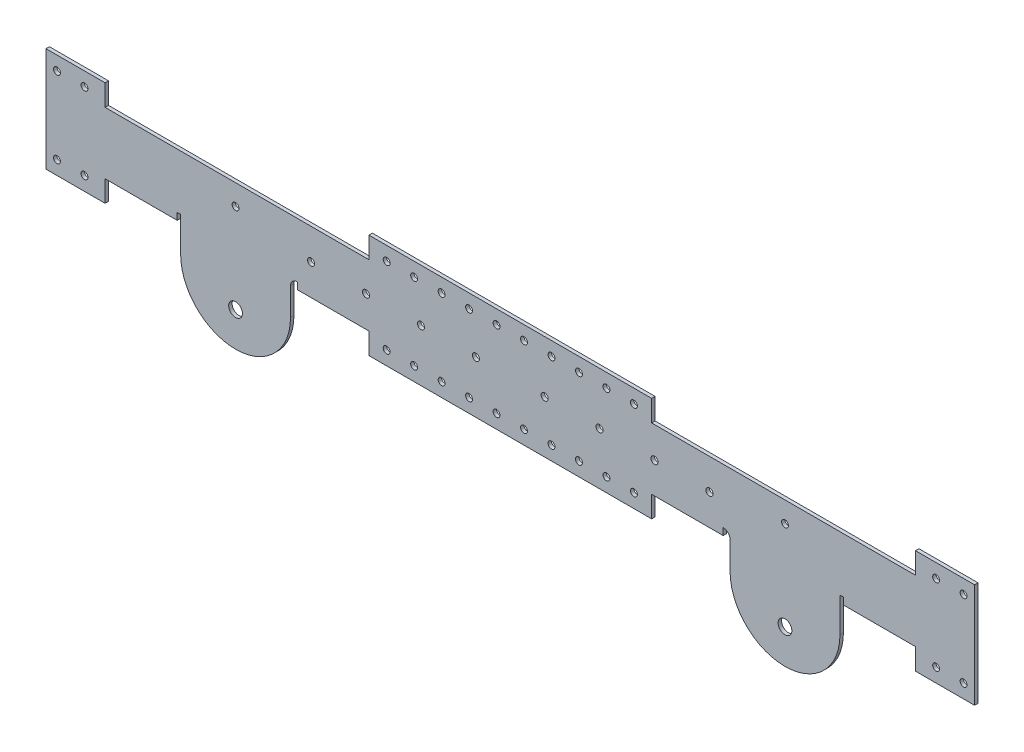
SolidWorks part; units mm, degrees
ref_plane "Front Plane" through (0, 0, 0) normal (0, 0, 1) x (1, 0, 0)
ref_plane "Top Plane" through (0, 0, 0) normal (0, 1, 0) x (1, 0, 0)
ref_plane "Right Plane" through (0, 0, 0) normal (1, 0, 0) x (0, 0, -1)
sketch "Sketch1" plane through (0, 0, 0) normal (0, 0, 1) x (1, 0, 0)
  line L0 (50.8, 0) -> (50.8, 25.4)
  line L1 (-50.8, 0) -> (-50.8, 76.2)
  line L2 (57.15, 31.75) -> (438.15, 31.75)
  line L3 (444.5, 25.4) -> (444.5, 0)
  line L4 (546.1, 0) -> (546.1, 76.2)
  line L5 (-50.8, 76.2) -> (546.1, 76.2)
  arc A0 (-50.8, 0) -> (50.8, 0) centre (0, 0) ccw
  arc A1 (50.8, 25.4) -> (57.15, 31.75) centre (57.15, 25.4) cw
  arc A2 (438.15, 31.75) -> (444.5, 25.4) centre (438.15, 25.4) cw
  arc A3 (444.5, 0) -> (546.1, 0) centre (495.3, 0) ccw
  circle A4 centre (0, 0) radius 6.35
  circle A5 centre (495.3, 0) radius 6.35
  dimension "D1" = 101.6
  dimension "D2" = 6.35
  dimension "D4" = 6.35
  dimension "D6" = 76.2
  dimension "D3" = 381
  dimension "D5" = 25.4
  dimension "D7" = 76.2
extrude "Boss-Extrude1" add sketch "Sketch1" along normal blind 3.175
sketch "Sketch2" plane through (0, 0, 3.175) normal (0, 0, 1) x (1, 0, 0)
  line L0 (-50.8, 76.2) -> (-50.8, 73.025)
  line L1 (-50.8, 76.2) -> (-50.8, 0) construction
  line L2 (546.1, 76.2) -> (-50.8, 76.2)
  line L3 (-50.8, 73.025) -> (546.1, 73.025)
  line L4 (546.1, 0) -> (546.1, 76.2) construction
  line L5 (546.1, 73.025) -> (546.1, 76.2)
  dimension "D1" = 3.175
extrude "Boss-Extrude2" add sketch "Sketch2" along normal blind 25.4
fillet "Fillet1" radius 2.54 2 edges at (247.65, 76.2, 0)
sketch "Sketch3" plane through (0, 76.2, 0) normal (0, 1, 0) x (1, 0, 0)
  line L0 (546.1, -28.575) -> (546.1, -2.54)
  circle A0 centre (527.05, -15.5575) radius 3.2639
  circle A1 centre (501.65, -15.5575) radius 3.2639
  circle A2 centre (476.25, -15.5575) radius 3.2639
  circle A3 centre (450.85, -15.5575) radius 3.2639
  circle A4 centre (425.45, -15.5575) radius 3.2639
  circle A5 centre (400.05, -15.5575) radius 3.2639
  circle A6 centre (374.65, -15.5575) radius 3.2639
  circle A7 centre (349.25, -15.5575) radius 3.2639
  circle A8 centre (323.85, -15.5575) radius 3.2639
  circle A9 centre (298.45, -15.5575) radius 3.2639
  circle A10 centre (273.05, -15.5575) radius 3.2639
  circle A11 centre (247.65, -15.5575) radius 3.2639
  circle A12 centre (222.25, -15.5575) radius 3.2639
  circle A13 centre (196.85, -15.5575) radius 3.2639
  circle A14 centre (171.45, -15.5575) radius 3.2639
  circle A15 centre (146.05, -15.5575) radius 3.2639
  circle A16 centre (120.65, -15.5575) radius 3.2639
  circle A17 centre (95.25, -15.5575) radius 3.2639
  circle A18 centre (69.85, -15.5575) radius 3.2639
  circle A19 centre (44.45, -15.5575) radius 3.2639
  circle A20 centre (19.05, -15.5575) radius 3.2639
  circle A21 centre (-6.35, -15.5575) radius 3.2639
  circle A22 centre (-31.75, -15.5575) radius 3.2639
  dimension "D1" = 19.05
  dimension "D2" = 23
extrude "Cut-Extrude1" cut sketch "Sketch3" against normal blind 25.4 contours A0 | A1 | A2 | A3 | A22 | A21 | A20 | A19 | A18 | A17 | A16 | A15 | A14 | A13 | A12 | A11 | A10 | A9 | A8 | A7 | A6 | A5 | A4 region at (527.05, 76.2, 15.5575) region at (501.65, 76.2, 15.5575) region at (476.25, 76.2, 15.5575) region at (450.85, 76.2, 15.5575) region at (425.45, 76.2, 15.5575) region at (400.05, 76.2, 15.5575) region at (374.65, 76.2, 15.5575) region at (349.25, 76.2, 15.5575) region at (323.85, 76.2, 15.5575) region at (298.45, 76.2, 15.5575) region at (273.05, 76.2, 15.5575) region at (247.65, 76.2, 15.5575) region at (222.25, 76.2, 15.5575) region at (196.85, 76.2, 15.5575) region at (171.45, 76.2, 15.5575) region at (146.05, 76.2, 15.5575) region at (120.65, 76.2, 15.5575) region at (95.25, 76.2, 15.5575) region at (69.85, 76.2, 15.5575) region at (44.45, 76.2, 15.5575) region at (19.05, 76.2, 15.5575) region at (-6.35, 76.2, 15.5575) region at (-31.75, 76.2, 15.5575)
sketch "Sketch5" plane through (0, 0, 0) normal (0, 0, -1) x (-1, 0, 0)
  line L0 (-444.5, 25.4) -> (-444.5, 0) construction
  circle A0 centre (-425.45, 53.975) radius 3.2639
  circle A1 centre (-374.65, 53.975) radius 3.2639
  circle A2 centre (-323.85, 53.975) radius 3.2639
  circle A3 centre (-273.05, 53.975) radius 3.2639
  circle A4 centre (-222.25, 53.975) radius 3.2639
  circle A5 centre (-171.45, 53.975) radius 3.2639
  circle A6 centre (-120.65, 53.975) radius 3.2639
  circle A7 centre (-69.85, 53.975) radius 3.2639
  dimension "D1" = 6.5278
  dimension "D2" = 19.05
  dimension "D3" = 8
extrude "Cut-Extrude2" cut sketch "Sketch5" against normal blind 25.4
sketch "Sketch6" plane through (0, 0, 3.175) normal (0, 0, 1) x (1, 0, 0)
  line L1 (-50.8, 76.2) -> (-82.55, 76.2)
  line L2 (-50.8, 76.2) -> (-50.8, 31.75)
  line L3 (-50.8, 31.75) -> (-82.55, 31.75)
  line L4 (-82.55, 76.2) -> (-82.55, 31.75)
  line L5 (546.1, 76.2) -> (577.85, 76.2)
  line L6 (546.1, 76.2) -> (546.1, 31.75)
  line L7 (546.1, 31.75) -> (577.85, 31.75)
  line L8 (577.85, 76.2) -> (577.85, 31.75)
  dimension "D1" = 31.75
  dimension "D2" = 31.75
extrude "Boss-Extrude3" add sketch "Sketch6" against normal blind 3.175
sketch "Sketch7" plane through (0, 0, 3.175) normal (0, 0, 1) x (1, 0, 0)
  line L1 (57.15, 31.75) -> (438.15, 31.75) construction
  line L2 (-50.8, 73.025) -> (-82.55, 73.025)
  line L3 (-50.8, 73.025) -> (-50.8, 76.2)
  line L4 (-50.8, 76.2) -> (-82.55, 76.2)
  line L5 (-82.55, 31.75) -> (-50.8, 31.75)
  line L6 (-82.55, 31.75) -> (-82.55, 34.925)
  line L7 (-82.55, 34.925) -> (-50.8, 34.925)
  line L8 (-50.8, 31.75) -> (-50.8, 34.925)
  line L9 (577.85, 31.75) -> (577.85, 76.2) construction
  line L10 (546.1, 76.2) -> (577.85, 76.2)
  line L11 (546.1, 76.2) -> (546.1, 73.025)
  line L12 (546.1, 73.025) -> (577.85, 73.025)
  line L13 (577.85, 76.2) -> (577.85, 73.025)
  line L14 (-82.55, 73.025) -> (-82.55, 76.2)
  line L15 (577.85, 31.75) -> (546.1, 31.75)
  line L16 (577.85, 31.75) -> (577.85, 34.925)
  line L17 (577.85, 34.925) -> (546.1, 34.925)
  line L18 (546.1, 31.75) -> (546.1, 34.925)
  line L19 (57.15, 31.75) -> (438.15, 31.75)
  line L20 (57.15, 31.75) -> (57.15, 34.925)
  line L21 (57.15, 34.925) -> (438.15, 34.925)
  line L22 (438.15, 31.75) -> (438.15, 34.925)
  arc A0 (57.15, 31.75) -> (50.8, 25.4) centre (57.15, 25.4) ccw construction
  dimension "D1" = 3.175
  dimension "D2" = 3.175
  dimension "D3" = 3.175
extrude "Boss-Extrude4" add sketch "Sketch7" along normal blind 25.4
fillet "Fillet2" radius 2.54 16 edges at (-50.8, 15.875, 0) (0, -50.8, 0) (50.8, 12.7, 0) (52.6599, 29.8901, 0) (546.1, 15.875, 0) (495.3, -50.8, 0) (444.5, 12.7, 0) (442.6401, 29.8901, 0) (-66.675, 34.925, 3.175) (-66.675, 31.75, 0) (247.65, 31.75, 0) (247.65, 34.925, 3.175) (561.975, 34.925, 3.175) (561.975, 31.75, 0) (561.975, 76.2, 0) (-66.675, 76.2, 0)
sketch "Sketch8" plane through (0, 76.2, 0) normal (0, 1, 0) x (1, 0, 0)
  circle A0 centre (-31.75, -15.5575) radius 3.2639 construction
  circle A1 centre (-31.75, -15.5575) radius 3.2639
  circle A2 centre (-57.15, -15.5575) radius 3.2639
  circle A3 centre (-31.75, -15.5575) radius 3.2639
  circle A4 centre (-6.35, -15.5575) radius 3.2639
  circle A5 centre (19.05, -15.5575) radius 3.2639
  circle A6 centre (44.45, -15.5575) radius 3.2639
  circle A7 centre (69.85, -15.5575) radius 3.2639
  circle A8 centre (95.25, -15.5575) radius 3.2639
  circle A9 centre (120.65, -15.5575) radius 3.2639
  circle A10 centre (146.05, -15.5575) radius 3.2639
  circle A11 centre (171.45, -15.5575) radius 3.2639
  circle A12 centre (196.85, -15.5575) radius 3.2639
  circle A13 centre (222.25, -15.5575) radius 3.2639
  circle A14 centre (247.65, -15.5575) radius 3.2639
  circle A15 centre (273.05, -15.5575) radius 3.2639
  circle A16 centre (298.45, -15.5575) radius 3.2639
  circle A17 centre (323.85, -15.5575) radius 3.2639
  circle A18 centre (349.25, -15.5575) radius 3.2639
  circle A19 centre (374.65, -15.5575) radius 3.2639
  circle A20 centre (400.05, -15.5575) radius 3.2639
  circle A21 centre (425.45, -15.5575) radius 3.2639
  circle A22 centre (450.85, -15.5575) radius 3.2639
  circle A23 centre (476.25, -15.5575) radius 3.2639
  circle A24 centre (501.65, -15.5575) radius 3.2639
  circle A25 centre (527.05, -15.5575) radius 3.2639
  circle A26 centre (-6.35, -15.5575) radius 3.2639
  circle A27 centre (19.05, -15.5575) radius 3.2639
  circle A28 centre (44.45, -15.5575) radius 3.2639
  circle A29 centre (69.85, -15.5575) radius 3.2639
  circle A30 centre (95.25, -15.5575) radius 3.2639
  circle A31 centre (120.65, -15.5575) radius 3.2639
  circle A32 centre (146.05, -15.5575) radius 3.2639
  circle A33 centre (171.45, -15.5575) radius 3.2639
  circle A34 centre (196.85, -15.5575) radius 3.2639
  circle A35 centre (222.25, -15.5575) radius 3.2639
  circle A36 centre (247.65, -15.5575) radius 3.2639
  circle A37 centre (273.05, -15.5575) radius 3.2639
  circle A38 centre (298.45, -15.5575) radius 3.2639
  circle A39 centre (323.85, -15.5575) radius 3.2639
  circle A40 centre (349.25, -15.5575) radius 3.2639
  circle A41 centre (374.65, -15.5575) radius 3.2639
  circle A42 centre (400.05, -15.5575) radius 3.2639
  circle A43 centre (425.45, -15.5575) radius 3.2639
  circle A44 centre (450.85, -15.5575) radius 3.2639
  circle A45 centre (476.25, -15.5575) radius 3.2639
  circle A46 centre (501.65, -15.5575) radius 3.2639
  circle A47 centre (527.05, -15.5575) radius 3.2639
  circle A48 centre (552.45, -15.5575) radius 3.2639
  circle M1 centre (425.45, -15.5575) radius 3.2639
  circle M2 centre (400.05, -15.5575) radius 3.2639
  circle M3 centre (374.65, -15.5575) radius 3.2639
  circle M4 centre (349.25, -15.5575) radius 3.2639
  circle M5 centre (323.85, -15.5575) radius 3.2639
  circle M6 centre (298.45, -15.5575) radius 3.2639
  circle M7 centre (273.05, -15.5575) radius 3.2639
  circle M8 centre (247.65, -15.5575) radius 3.2639
  circle M9 centre (222.25, -15.5575) radius 3.2639
  circle M10 centre (196.85, -15.5575) radius 3.2639
  circle M11 centre (171.45, -15.5575) radius 3.2639
  circle M12 centre (146.05, -15.5575) radius 3.2639
  circle M13 centre (120.65, -15.5575) radius 3.2639
  circle M14 centre (95.25, -15.5575) radius 3.2639
  circle M15 centre (69.85, -15.5575) radius 3.2639
  circle M16 centre (44.45, -15.5575) radius 3.2639
  circle M17 centre (19.05, -15.5575) radius 3.2639
  circle M18 centre (-6.35, -15.5575) radius 3.2639
  circle M19 centre (-31.75, -15.5575) radius 3.2639
  circle M20 centre (450.85, -15.5575) radius 3.2639
  circle M21 centre (476.25, -15.5575) radius 3.2639
  circle M22 centre (501.65, -15.5575) radius 3.2639
  circle M23 centre (527.05, -15.5575) radius 3.2639
  dimension "D1" = 2
  dimension "D2" = 24
extrude "Cut-Extrude3" cut sketch "Sketch8" against normal blind 177.8 contours A2 | M19 | M18 | M17 | M16 | M15 | M14 | M13 | M12 | M11 | M10 | M9 | M8 | M7 | M6 | M5 | M4 | M3 | M2 | M1 | M20 | M21 | A48 | M23 | M22 region at (-31.75, 76.2, 15.5575) region at (-57.15, 76.2, 15.5575) region at (-6.35, 76.2, 15.5575) region at (19.05, 76.2, 15.5575) region at (44.45, 76.2, 15.5575) region at (69.85, 76.2, 15.5575) region at (95.25, 76.2, 15.5575) region at (120.65, 76.2, 15.5575) region at (146.05, 76.2, 15.5575) region at (171.45, 76.2, 15.5575) region at (196.85, 76.2, 15.5575) region at (222.25, 76.2, 15.5575) region at (247.65, 76.2, 15.5575) region at (273.05, 76.2, 15.5575) region at (298.45, 76.2, 15.5575) region at (323.85, 76.2, 15.5575) region at (349.25, 76.2, 15.5575) region at (374.65, 76.2, 15.5575) region at (400.05, 76.2, 15.5575) region at (425.45, 76.2, 15.5575) region at (450.85, 76.2, 15.5575) region at (476.25, 76.2, 15.5575) region at (501.65, 76.2, 15.5575) region at (527.05, 76.2, 15.5575) region at (552.45, 76.2, 15.5575)
sketch "Sketch9" plane through (0, 76.2, 0) normal (0, 1, 0) x (1, 0, 0)
  line L0 (-82.55, -28.575) -> (298.45, -28.575)
  line L1 (577.85, -28.575) -> (-82.55, -28.575) construction
  line L3 (298.45, -28.575) -> (746.3929, -28.575)
  line L4 (298.45, -28.575) -> (298.45, 89.0041)
  line L5 (298.45, 89.0041) -> (746.3929, 89.0041)
  line L6 (746.3929, -28.575) -> (746.3929, 89.0041)
  circle M1 centre (552.45, -15.5575) radius 3.2639
  circle M3 centre (425.45, -15.5575) radius 3.2639
  circle M4 centre (400.05, -15.5575) radius 3.2639
  circle M5 centre (374.65, -15.5575) radius 3.2639
  circle M6 centre (349.25, -15.5575) radius 3.2639
  circle M7 centre (323.85, -15.5575) radius 3.2639
  circle M8 centre (298.45, -15.5575) radius 3.2639
  circle M22 centre (450.85, -15.5575) radius 3.2639
  circle M23 centre (476.25, -15.5575) radius 3.2639
  circle M24 centre (501.65, -15.5575) radius 3.2639
  circle M25 centre (527.05, -15.5575) radius 3.2639
  line M26 (577.85, -28.575) -> (577.85, -2.54)
  line M27 (577.85, -2.54) -> (546.1, -2.54)
  line M28 (546.1, -2.54) -> (-50.8, -2.54)
  line M31 (-82.55, -28.575) -> (577.85, -28.575)
extrude "Cut-Extrude5" cut sketch "Sketch9" against normal blind 432.308 contours L4 M31 M26 M27 M28 M8 M4 M6 M22 M24 M25 M23 M7 M5 M3 M1 | L3 L6 L5 L4 M28 M27 M26 region at (438.4843, 76.2, 15.5575) region at (535.9254, 76.2, -37.5492)
mirror "Mirror4" about plane through (298.45, -356.108, 0) normal (1, 0, 0) of bodies 110
sketch "Sketch10" plane through (-82.55, 0, 0) normal (-1, 0, 0) x (0, 0, 1)
  line L8 (0, 73.66) -> (0, 34.29)
  line L9 (2.54, 31.75) -> (28.575, 31.75)
  line L10 (28.575, 31.75) -> (28.575, 34.925)
  line L11 (28.575, 34.925) -> (5.715, 34.925)
  line L12 (3.175, 37.465) -> (3.175, 73.025)
  line L13 (3.175, 73.025) -> (28.575, 73.025)
  line L14 (28.575, 73.025) -> (28.575, 76.2)
  line L15 (28.575, 76.2) -> (2.54, 76.2)
  line L16 (0, 73.66) -> (0, 34.29)
  line L17 (2.54, 31.75) -> (28.575, 31.75)
  line L18 (28.575, 31.75) -> (28.575, 34.925)
  line L19 (28.575, 34.925) -> (5.715, 34.925)
  line L20 (3.175, 37.465) -> (3.175, 73.025)
  line L21 (3.175, 73.025) -> (28.575, 73.025)
  line L22 (28.575, 73.025) -> (28.575, 76.2)
  line L23 (28.575, 76.2) -> (2.54, 76.2)
  arc A3 (0, 34.29) -> (2.54, 31.75) centre (2.54, 34.29) ccw
  arc A4 (3.175, 37.465) -> (5.715, 34.925) centre (5.715, 37.465) ccw
  arc A5 (2.54, 76.2) -> (0, 73.66) centre (2.54, 73.66) ccw
  arc A6 (0, 34.29) -> (2.54, 31.75) centre (2.54, 34.29) ccw
  arc A7 (3.175, 37.465) -> (5.715, 34.925) centre (5.715, 37.465) ccw
  arc A8 (2.54, 76.2) -> (0, 73.66) centre (2.54, 73.66) ccw
  dimension "D1" = 0
extrude "Boss-Extrude6" add sketch "Sketch10" along normal blind 66.675
sketch "Sketch11" plane through (679.45, 0, 0) normal (1, 0, 0) x (0, 0, -1)
  line L8 (0, 34.29) -> (0, 73.66)
  line L9 (-2.54, 76.2) -> (-28.575, 76.2)
  line L10 (-28.575, 76.2) -> (-28.575, 73.025)
  line L11 (-28.575, 73.025) -> (-3.175, 73.025)
  line L12 (-3.175, 73.025) -> (-3.175, 37.465)
  line L13 (-5.715, 34.925) -> (-28.575, 34.925)
  line L14 (-28.575, 34.925) -> (-28.575, 31.75)
  line L15 (-28.575, 31.75) -> (-2.54, 31.75)
  line L16 (0, 34.29) -> (0, 73.66)
  line L17 (-2.54, 76.2) -> (-28.575, 76.2)
  line L18 (-28.575, 76.2) -> (-28.575, 73.025)
  line L19 (-28.575, 73.025) -> (-3.175, 73.025)
  line L20 (-3.175, 73.025) -> (-3.175, 37.465)
  line L21 (-5.715, 34.925) -> (-28.575, 34.925)
  line L22 (-28.575, 34.925) -> (-28.575, 31.75)
  line L23 (-28.575, 31.75) -> (-2.54, 31.75)
  arc A3 (0, 73.66) -> (-2.54, 76.2) centre (-2.54, 73.66) ccw
  arc A4 (-5.715, 34.925) -> (-3.175, 37.465) centre (-5.715, 37.465) ccw
  arc A5 (-2.54, 31.75) -> (0, 34.29) centre (-2.54, 34.29) ccw
  arc A6 (0, 73.66) -> (-2.54, 76.2) centre (-2.54, 73.66) ccw
  arc A7 (-5.715, 34.925) -> (-3.175, 37.465) centre (-5.715, 37.465) ccw
  arc A8 (-2.54, 31.75) -> (0, 34.29) centre (-2.54, 34.29) ccw
  dimension "D1" = 0
extrude "Boss-Extrude7" add sketch "Sketch11" along normal blind 66.675
sketch "Sketch12" plane through (0, 0, 3.175) normal (0, 0, 1) x (1, 0, 0)
  line L1 (114.3, 114.3) -> (-114.3, 114.3)
  line L2 (460.9211, 135.1062) -> (717.55, 135.1062)
  line L3 (460.9211, 135.1062) -> (460.9211, -117.6098)
  line L4 (482.6, 135.1062) -> (692.7253, 135.1062)
  line L5 (692.7253, 135.1062) -> (711.2, 135.1062)
  line L6 (460.9211, -117.6098) -> (717.55, -117.6098)
  line L7 (717.55, 135.1062) -> (717.55, -117.6098)
  line L8 (482.6, 135.1062) -> (460.9211, 135.1062)
  line L11 (460.9211, 135.1062) -> (460.9211, -59.2459)
  line L12 (711.2, 135.1062) -> (717.55, 135.1062)
  line L15 (717.55, 135.1062) -> (717.55, 3.7539)
  line L16 (114.3, 114.3) -> (135.9789, 114.3)
  line L17 (114.3, 0) -> (114.3, -15.4588)
  line L18 (114.3, -15.4588) -> (135.9789, -15.4588)
  line L19 (135.9789, 114.3) -> (135.9789, -15.4588)
  line L20 (-114.3, 114.3) -> (-120.65, 114.3)
  line L21 (-114.3, 0) -> (-114.3, -7.9863)
  line L22 (-114.3, -7.9863) -> (-120.65, -7.9863)
  line L23 (-120.65, 114.3) -> (-120.65, -7.9863)
  arc A0 (-114.3, 0) -> (114.3, 0) centre (0, 0) ccw
  circle M1 centre (0, 0) radius 6.35
  circle M5 centre (120.65, 53.975) radius 3.2639
  circle M6 centre (69.85, 53.975) radius 3.2639
  line M7 (57.15, 37.465) -> (539.75, 37.465)
  line M8 (539.75, 37.465) -> (539.75, 31.75)
  arc M9 (539.75, 31.75) -> (546.1, 25.4) centre (539.75, 25.4) cw
  line M10 (546.1, 25.4) -> (546.1, 0)
  arc M11 (546.1, 0) -> (647.7, 0) centre (596.9, 0) ccw
  line M12 (647.7, 0) -> (647.7, 31.75)
  line M13 (647.7, 31.75) -> (647.7, 37.465)
  line M14 (647.7, 37.465) -> (746.125, 37.465)
  line M16 (746.125, 73.025) -> (647.7, 73.025)
  line M17 (647.7, 73.025) -> (647.7, 70.485)
  line M18 (647.7, 70.485) -> (-50.8, 70.485)
  line M19 (-50.8, 70.485) -> (-50.8, 73.025)
  line M20 (-50.8, 73.025) -> (-149.225, 73.025)
  line M22 (-149.225, 37.465) -> (-50.8, 37.465)
  line M23 (-50.8, 37.465) -> (-50.8, 31.75)
  line M24 (-50.8, 31.75) -> (-50.8, 0)
  arc M25 (-50.8, 0) -> (50.8, 0) centre (0, 0) ccw
  line M26 (50.8, 0) -> (50.8, 25.4)
  arc M27 (50.8, 25.4) -> (57.15, 31.75) centre (57.15, 25.4) cw
  line M28 (57.15, 31.75) -> (57.15, 37.465)
  circle M29 centre (596.9, 0) radius 6.35
  circle M33 centre (476.25, 53.975) radius 3.2639
  circle M34 centre (527.05, 53.975) radius 3.2639
  dimension "D1" = 13.335
  dimension "D2" = 6.35
  dimension "D3" = 13.335
  dimension "D4" = 6.35
extrude "Cut-Extrude8" cut sketch "Sketch12" along normal blind 66.675 contours L7 L3 L6 M14 M13 M12 M11 M10 M9 M8 M7 | L7 L3 M16 M17 M18 M7 M8 M9 M10 M11 M12 M13 M14 M34 M33 M29 | L7 L2 L3 M18 M17 M16 | L21 A0 L17 L18 L19 L23 L22 M7 M28 M27 M26 M25 M24 M23 M22 | L23 L19 M20 M22 M23 M24 M25 M26 M27 M28 M7 M18 M19 M6 M5 M1 | L20 L23 L19 L16 L1 M20 M19 M18 region at (9.1616, 92.7234, 3.175) region at (2.7974, 27.6189, 3.175) region at (132.9974, 11.0031, 3.175) region at (594.1026, 27.6189, 3.175) region at (588.2256, 103.1313, 3.175) region at (500.3355, 34.4666, 3.175)
sketch "Sketch13" plane through (0, 76.2, 0) normal (0, 1, 0) x (1, 0, 0)
  circle A0 centre (146.05, -15.5575) radius 3.2639 construction
  circle A1 centre (146.05, -15.5575) radius 3.2639
sketch "Sketch14" plane through (746.125, 0, 0) normal (1, 0, 0) x (0, 0, -1)
  line L8 (0, 34.29) -> (0, 73.66)
  line L9 (-2.54, 76.2) -> (-28.575, 76.2)
  line L10 (-28.575, 76.2) -> (-28.575, 73.025)
  line L11 (-28.575, 73.025) -> (-3.175, 73.025)
  line L12 (-3.175, 73.025) -> (-3.175, 37.465)
  line L13 (-5.715, 34.925) -> (-28.575, 34.925)
  line L14 (-28.575, 34.925) -> (-28.575, 31.75)
  line L15 (-28.575, 31.75) -> (-2.54, 31.75)
  line L16 (0, 34.29) -> (0, 73.66)
  line L17 (-2.54, 76.2) -> (-28.575, 76.2)
  line L18 (-28.575, 76.2) -> (-28.575, 73.025)
  line L19 (-28.575, 73.025) -> (-3.175, 73.025)
  line L20 (-3.175, 73.025) -> (-3.175, 37.465)
  line L21 (-5.715, 34.925) -> (-28.575, 34.925)
  line L22 (-28.575, 34.925) -> (-28.575, 31.75)
  line L23 (-28.575, 31.75) -> (-2.54, 31.75)
  arc A3 (-2.54, 31.75) -> (0, 34.29) centre (-2.54, 34.29) ccw
  arc A4 (0, 73.66) -> (-2.54, 76.2) centre (-2.54, 73.66) ccw
  arc A5 (-5.715, 34.925) -> (-3.175, 37.465) centre (-5.715, 37.465) ccw
  arc A6 (-2.54, 31.75) -> (0, 34.29) centre (-2.54, 34.29) ccw
  arc A7 (0, 73.66) -> (-2.54, 76.2) centre (-2.54, 73.66) ccw
  arc A8 (-5.715, 34.925) -> (-3.175, 37.465) centre (-5.715, 37.465) ccw
  dimension "D1" = 0
extrude "Boss-Extrude8" add sketch "Sketch14" along normal blind 19.05
sketch "Sketch15" plane through (-149.225, 0, 0) normal (-1, 0, 0) x (0, 0, 1)
  line L8 (0, 73.66) -> (0, 34.29)
  line L9 (2.54, 31.75) -> (28.575, 31.75)
  line L10 (28.575, 31.75) -> (28.575, 34.925)
  line L11 (28.575, 34.925) -> (5.715, 34.925)
  line L12 (3.175, 37.465) -> (3.175, 73.025)
  line L13 (3.175, 73.025) -> (28.575, 73.025)
  line L14 (28.575, 73.025) -> (28.575, 76.2)
  line L15 (28.575, 76.2) -> (2.54, 76.2)
  line L16 (0, 73.66) -> (0, 34.29)
  line L17 (2.54, 31.75) -> (28.575, 31.75)
  line L18 (28.575, 31.75) -> (28.575, 34.925)
  line L19 (28.575, 34.925) -> (5.715, 34.925)
  line L20 (3.175, 37.465) -> (3.175, 73.025)
  line L21 (3.175, 73.025) -> (28.575, 73.025)
  line L22 (28.575, 73.025) -> (28.575, 76.2)
  line L23 (28.575, 76.2) -> (2.54, 76.2)
  arc A3 (2.54, 76.2) -> (0, 73.66) centre (2.54, 73.66) ccw
  arc A4 (0, 34.29) -> (2.54, 31.75) centre (2.54, 34.29) ccw
  arc A5 (3.175, 37.465) -> (5.715, 34.925) centre (5.715, 37.465) ccw
  arc A6 (2.54, 76.2) -> (0, 73.66) centre (2.54, 73.66) ccw
  arc A7 (0, 34.29) -> (2.54, 31.75) centre (2.54, 34.29) ccw
  arc A8 (3.175, 37.465) -> (5.715, 34.925) centre (5.715, 37.465) ccw
  dimension "D1" = 0
extrude "Boss-Extrude9" add sketch "Sketch15" along normal blind 19.05
sketch "Sketch16" plane through (0, 76.2, 0) normal (0, 1, 0) x (1, 0, 0)
  circle A0 centre (146.05, -15.5575) radius 3.2639 construction
  circle A1 centre (146.05, -15.5575) radius 3.2639
  circle A2 centre (171.45, -15.5575) radius 3.2639
  circle A3 centre (196.85, -15.5575) radius 3.2639
  circle A4 centre (222.25, -15.5575) radius 3.2639
  circle A5 centre (247.65, -15.5575) radius 3.2639
  circle A6 centre (273.05, -15.5575) radius 3.2639
  circle A7 centre (298.45, -15.5575) radius 3.2639
  circle A8 centre (323.85, -15.5575) radius 3.2639
  circle A9 centre (349.25, -15.5575) radius 3.2639
  circle A10 centre (374.65, -15.5575) radius 3.2639
  circle A11 centre (400.05, -15.5575) radius 3.2639
  circle A12 centre (425.45, -15.5575) radius 3.2639
  circle A13 centre (450.85, -15.5575) radius 3.2639
  circle A14 centre (476.25, -15.5575) radius 3.2639
  circle A15 centre (501.65, -15.5575) radius 3.2639
  circle A16 centre (527.05, -15.5575) radius 3.2639
  circle A17 centre (552.45, -15.5575) radius 3.2639
  circle A18 centre (577.85, -15.5575) radius 3.2639
  circle A19 centre (603.25, -15.5575) radius 3.2639
  circle A20 centre (628.65, -15.5575) radius 3.2639
  circle A21 centre (654.05, -15.5575) radius 3.2639
  circle A22 centre (679.45, -15.5575) radius 3.2639
  circle A23 centre (704.85, -15.5575) radius 3.2639
  circle A24 centre (730.25, -15.5575) radius 3.2639
  circle A25 centre (755.65, -15.5575) radius 3.2639
  circle A26 centre (146.05, -15.5575) radius 3.2639
  circle A27 centre (171.45, -15.5575) radius 3.2639
  circle A28 centre (196.85, -15.5575) radius 3.2639
  circle A29 centre (222.25, -15.5575) radius 3.2639
  circle A30 centre (247.65, -15.5575) radius 3.2639
  circle A31 centre (273.05, -15.5575) radius 3.2639
  circle A32 centre (298.45, -15.5575) radius 3.2639
  circle A33 centre (323.85, -15.5575) radius 3.2639
  circle A34 centre (349.25, -15.5575) radius 3.2639
  circle A35 centre (374.65, -15.5575) radius 3.2639
  circle A36 centre (400.05, -15.5575) radius 3.2639
  circle A37 centre (425.45, -15.5575) radius 3.2639
  circle A38 centre (450.85, -15.5575) radius 3.2639
  circle A39 centre (476.25, -15.5575) radius 3.2639
  circle A40 centre (501.65, -15.5575) radius 3.2639
  circle A41 centre (527.05, -15.5575) radius 3.2639
  circle A42 centre (552.45, -15.5575) radius 3.2639
  circle A43 centre (577.85, -15.5575) radius 3.2639
  circle A44 centre (603.25, -15.5575) radius 3.2639
  circle A45 centre (628.65, -15.5575) radius 3.2639
  circle A46 centre (654.05, -15.5575) radius 3.2639
  circle A47 centre (679.45, -15.5575) radius 3.2639
  circle A48 centre (704.85, -15.5575) radius 3.2639
  circle A49 centre (730.25, -15.5575) radius 3.2639
  circle A50 centre (120.65, -15.5575) radius 3.2639
  circle A51 centre (146.05, -15.5575) radius 3.2639
  circle A52 centre (171.45, -15.5575) radius 3.2639
  circle A53 centre (196.85, -15.5575) radius 3.2639
  circle A54 centre (222.25, -15.5575) radius 3.2639
  circle A55 centre (247.65, -15.5575) radius 3.2639
  circle A56 centre (273.05, -15.5575) radius 3.2639
  circle A57 centre (298.45, -15.5575) radius 3.2639
  circle A58 centre (323.85, -15.5575) radius 3.2639
  circle A59 centre (349.25, -15.5575) radius 3.2639
  circle A60 centre (374.65, -15.5575) radius 3.2639
  circle A61 centre (400.05, -15.5575) radius 3.2639
  circle A62 centre (425.45, -15.5575) radius 3.2639
  circle A63 centre (450.85, -15.5575) radius 3.2639
  circle A64 centre (476.25, -15.5575) radius 3.2639
  circle A65 centre (501.65, -15.5575) radius 3.2639
  circle A66 centre (527.05, -15.5575) radius 3.2639
  circle A67 centre (552.45, -15.5575) radius 3.2639
  circle A68 centre (577.85, -15.5575) radius 3.2639
  circle A69 centre (603.25, -15.5575) radius 3.2639
  circle A70 centre (628.65, -15.5575) radius 3.2639
  circle A71 centre (654.05, -15.5575) radius 3.2639
  circle A72 centre (679.45, -15.5575) radius 3.2639
  circle A73 centre (704.85, -15.5575) radius 3.2639
  circle A74 centre (95.25, -15.5575) radius 3.2639
  circle A75 centre (120.65, -15.5575) radius 3.2639
  circle A76 centre (146.05, -15.5575) radius 3.2639
  circle A77 centre (171.45, -15.5575) radius 3.2639
  circle A78 centre (196.85, -15.5575) radius 3.2639
  circle A79 centre (222.25, -15.5575) radius 3.2639
  circle A80 centre (247.65, -15.5575) radius 3.2639
  circle A81 centre (273.05, -15.5575) radius 3.2639
  circle A82 centre (298.45, -15.5575) radius 3.2639
  circle A83 centre (323.85, -15.5575) radius 3.2639
  circle A84 centre (349.25, -15.5575) radius 3.2639
  circle A85 centre (374.65, -15.5575) radius 3.2639
  circle A86 centre (400.05, -15.5575) radius 3.2639
  circle A87 centre (425.45, -15.5575) radius 3.2639
  circle A88 centre (450.85, -15.5575) radius 3.2639
  circle A89 centre (476.25, -15.5575) radius 3.2639
  circle A90 centre (501.65, -15.5575) radius 3.2639
  circle A91 centre (527.05, -15.5575) radius 3.2639
  circle A92 centre (552.45, -15.5575) radius 3.2639
  circle A93 centre (577.85, -15.5575) radius 3.2639
  circle A94 centre (603.25, -15.5575) radius 3.2639
  circle A95 centre (628.65, -15.5575) radius 3.2639
  circle A96 centre (654.05, -15.5575) radius 3.2639
  circle A97 centre (679.45, -15.5575) radius 3.2639
  circle A98 centre (69.85, -15.5575) radius 3.2639
  circle A99 centre (95.25, -15.5575) radius 3.2639
  circle A100 centre (120.65, -15.5575) radius 3.2639
  circle A101 centre (146.05, -15.5575) radius 3.2639
  circle A102 centre (171.45, -15.5575) radius 3.2639
  circle A103 centre (196.85, -15.5575) radius 3.2639
  circle A104 centre (222.25, -15.5575) radius 3.2639
  circle A105 centre (247.65, -15.5575) radius 3.2639
  circle A106 centre (273.05, -15.5575) radius 3.2639
  circle A107 centre (298.45, -15.5575) radius 3.2639
  circle A108 centre (323.85, -15.5575) radius 3.2639
  circle A109 centre (349.25, -15.5575) radius 3.2639
  circle A110 centre (374.65, -15.5575) radius 3.2639
  circle A111 centre (400.05, -15.5575) radius 3.2639
  circle A112 centre (425.45, -15.5575) radius 3.2639
  circle A113 centre (450.85, -15.5575) radius 3.2639
  circle A114 centre (476.25, -15.5575) radius 3.2639
  circle A115 centre (501.65, -15.5575) radius 3.2639
  circle A116 centre (527.05, -15.5575) radius 3.2639
  circle A117 centre (552.45, -15.5575) radius 3.2639
  circle A118 centre (577.85, -15.5575) radius 3.2639
  circle A119 centre (603.25, -15.5575) radius 3.2639
  circle A120 centre (628.65, -15.5575) radius 3.2639
  circle A121 centre (654.05, -15.5575) radius 3.2639
  circle A122 centre (44.45, -15.5575) radius 3.2639
  circle A123 centre (69.85, -15.5575) radius 3.2639
  circle A124 centre (95.25, -15.5575) radius 3.2639
  circle A125 centre (120.65, -15.5575) radius 3.2639
  circle A126 centre (146.05, -15.5575) radius 3.2639
  circle A127 centre (171.45, -15.5575) radius 3.2639
  circle A128 centre (196.85, -15.5575) radius 3.2639
  circle A129 centre (222.25, -15.5575) radius 3.2639
  circle A130 centre (247.65, -15.5575) radius 3.2639
  circle A131 centre (273.05, -15.5575) radius 3.2639
  circle A132 centre (298.45, -15.5575) radius 3.2639
  circle A133 centre (323.85, -15.5575) radius 3.2639
  circle A134 centre (349.25, -15.5575) radius 3.2639
  circle A135 centre (374.65, -15.5575) radius 3.2639
  circle A136 centre (400.05, -15.5575) radius 3.2639
  circle A137 centre (425.45, -15.5575) radius 3.2639
  circle A138 centre (450.85, -15.5575) radius 3.2639
  circle A139 centre (476.25, -15.5575) radius 3.2639
  circle A140 centre (501.65, -15.5575) radius 3.2639
  circle A141 centre (527.05, -15.5575) radius 3.2639
  circle A142 centre (552.45, -15.5575) radius 3.2639
  circle A143 centre (577.85, -15.5575) radius 3.2639
  circle A144 centre (603.25, -15.5575) radius 3.2639
  circle A145 centre (628.65, -15.5575) radius 3.2639
  circle A146 centre (19.05, -15.5575) radius 3.2639
  circle A147 centre (44.45, -15.5575) radius 3.2639
  circle A148 centre (69.85, -15.5575) radius 3.2639
  circle A149 centre (95.25, -15.5575) radius 3.2639
  circle A150 centre (120.65, -15.5575) radius 3.2639
  circle A151 centre (146.05, -15.5575) radius 3.2639
  circle A152 centre (171.45, -15.5575) radius 3.2639
  circle A153 centre (196.85, -15.5575) radius 3.2639
  circle A154 centre (222.25, -15.5575) radius 3.2639
  circle A155 centre (247.65, -15.5575) radius 3.2639
  circle A156 centre (273.05, -15.5575) radius 3.2639
  circle A157 centre (298.45, -15.5575) radius 3.2639
  circle A158 centre (323.85, -15.5575) radius 3.2639
  circle A159 centre (349.25, -15.5575) radius 3.2639
  circle A160 centre (374.65, -15.5575) radius 3.2639
  circle A161 centre (400.05, -15.5575) radius 3.2639
  circle A162 centre (425.45, -15.5575) radius 3.2639
  circle A163 centre (450.85, -15.5575) radius 3.2639
  circle A164 centre (476.25, -15.5575) radius 3.2639
  circle A165 centre (501.65, -15.5575) radius 3.2639
  circle A166 centre (527.05, -15.5575) radius 3.2639
  circle A167 centre (552.45, -15.5575) radius 3.2639
  circle A168 centre (577.85, -15.5575) radius 3.2639
  circle A169 centre (603.25, -15.5575) radius 3.2639
  circle A170 centre (-6.35, -15.5575) radius 3.2639
  circle A171 centre (19.05, -15.5575) radius 3.2639
  circle A172 centre (44.45, -15.5575) radius 3.2639
  circle A173 centre (69.85, -15.5575) radius 3.2639
  circle A174 centre (95.25, -15.5575) radius 3.2639
  circle A175 centre (120.65, -15.5575) radius 3.2639
  circle A176 centre (146.05, -15.5575) radius 3.2639
  circle A177 centre (171.45, -15.5575) radius 3.2639
  circle A178 centre (196.85, -15.5575) radius 3.2639
  circle A179 centre (222.25, -15.5575) radius 3.2639
  circle A180 centre (247.65, -15.5575) radius 3.2639
  circle A181 centre (273.05, -15.5575) radius 3.2639
  circle A182 centre (298.45, -15.5575) radius 3.2639
  circle A183 centre (323.85, -15.5575) radius 3.2639
  circle A184 centre (349.25, -15.5575) radius 3.2639
  circle A185 centre (374.65, -15.5575) radius 3.2639
  circle A186 centre (400.05, -15.5575) radius 3.2639
  circle A187 centre (425.45, -15.5575) radius 3.2639
  circle A188 centre (450.85, -15.5575) radius 3.2639
  circle A189 centre (476.25, -15.5575) radius 3.2639
  circle A190 centre (501.65, -15.5575) radius 3.2639
  circle A191 centre (527.05, -15.5575) radius 3.2639
  circle A192 centre (552.45, -15.5575) radius 3.2639
  circle A193 centre (577.85, -15.5575) radius 3.2639
  circle A194 centre (-31.75, -15.5575) radius 3.2639
  circle A195 centre (-6.35, -15.5575) radius 3.2639
  circle A196 centre (19.05, -15.5575) radius 3.2639
  circle A197 centre (44.45, -15.5575) radius 3.2639
  circle A198 centre (69.85, -15.5575) radius 3.2639
  circle A199 centre (95.25, -15.5575) radius 3.2639
  circle A200 centre (120.65, -15.5575) radius 3.2639
  circle A201 centre (146.05, -15.5575) radius 3.2639
  circle A202 centre (171.45, -15.5575) radius 3.2639
  circle A203 centre (196.85, -15.5575) radius 3.2639
  circle A204 centre (222.25, -15.5575) radius 3.2639
  circle A205 centre (247.65, -15.5575) radius 3.2639
  circle A206 centre (273.05, -15.5575) radius 3.2639
  circle A207 centre (298.45, -15.5575) radius 3.2639
  circle A208 centre (323.85, -15.5575) radius 3.2639
  circle A209 centre (349.25, -15.5575) radius 3.2639
  circle A210 centre (374.65, -15.5575) radius 3.2639
  circle A211 centre (400.05, -15.5575) radius 3.2639
  circle A212 centre (425.45, -15.5575) radius 3.2639
  circle A213 centre (450.85, -15.5575) radius 3.2639
  circle A214 centre (476.25, -15.5575) radius 3.2639
  circle A215 centre (501.65, -15.5575) radius 3.2639
  circle A216 centre (527.05, -15.5575) radius 3.2639
  circle A217 centre (552.45, -15.5575) radius 3.2639
  circle A218 centre (-57.15, -15.5575) radius 3.2639
  circle A219 centre (-31.75, -15.5575) radius 3.2639
  circle A220 centre (-6.35, -15.5575) radius 3.2639
  circle A221 centre (19.05, -15.5575) radius 3.2639
  circle A222 centre (44.45, -15.5575) radius 3.2639
  circle A223 centre (69.85, -15.5575) radius 3.2639
  circle A224 centre (95.25, -15.5575) radius 3.2639
  circle A225 centre (120.65, -15.5575) radius 3.2639
  circle A226 centre (146.05, -15.5575) radius 3.2639
  circle A227 centre (171.45, -15.5575) radius 3.2639
  circle A228 centre (196.85, -15.5575) radius 3.2639
  circle A229 centre (222.25, -15.5575) radius 3.2639
  circle A230 centre (247.65, -15.5575) radius 3.2639
  circle A231 centre (273.05, -15.5575) radius 3.2639
  circle A232 centre (298.45, -15.5575) radius 3.2639
  circle A233 centre (323.85, -15.5575) radius 3.2639
  circle A234 centre (349.25, -15.5575) radius 3.2639
  circle A235 centre (374.65, -15.5575) radius 3.2639
  circle A236 centre (400.05, -15.5575) radius 3.2639
  circle A237 centre (425.45, -15.5575) radius 3.2639
  circle A238 centre (450.85, -15.5575) radius 3.2639
  circle A239 centre (476.25, -15.5575) radius 3.2639
  circle A240 centre (501.65, -15.5575) radius 3.2639
  circle A241 centre (527.05, -15.5575) radius 3.2639
  circle A242 centre (-82.55, -15.5575) radius 3.2639
  circle A243 centre (-57.15, -15.5575) radius 3.2639
  circle A244 centre (-31.75, -15.5575) radius 3.2639
  circle A245 centre (-6.35, -15.5575) radius 3.2639
  circle A246 centre (19.05, -15.5575) radius 3.2639
  circle A247 centre (44.45, -15.5575) radius 3.2639
  circle A248 centre (69.85, -15.5575) radius 3.2639
  circle A249 centre (95.25, -15.5575) radius 3.2639
  circle A250 centre (120.65, -15.5575) radius 3.2639
  circle A251 centre (146.05, -15.5575) radius 3.2639
  circle A252 centre (171.45, -15.5575) radius 3.2639
  circle A253 centre (196.85, -15.5575) radius 3.2639
  circle A254 centre (222.25, -15.5575) radius 3.2639
  circle A255 centre (247.65, -15.5575) radius 3.2639
  circle A256 centre (273.05, -15.5575) radius 3.2639
  circle A257 centre (298.45, -15.5575) radius 3.2639
  circle A258 centre (323.85, -15.5575) radius 3.2639
  circle A259 centre (349.25, -15.5575) radius 3.2639
  circle A260 centre (374.65, -15.5575) radius 3.2639
  circle A261 centre (400.05, -15.5575) radius 3.2639
  circle A262 centre (425.45, -15.5575) radius 3.2639
  circle A263 centre (450.85, -15.5575) radius 3.2639
  circle A264 centre (476.25, -15.5575) radius 3.2639
  circle A265 centre (501.65, -15.5575) radius 3.2639
  circle A266 centre (-107.95, -15.5575) radius 3.2639
  circle A267 centre (-82.55, -15.5575) radius 3.2639
  circle A268 centre (-57.15, -15.5575) radius 3.2639
  circle A269 centre (-31.75, -15.5575) radius 3.2639
  circle A270 centre (-6.35, -15.5575) radius 3.2639
  circle A271 centre (19.05, -15.5575) radius 3.2639
  circle A272 centre (44.45, -15.5575) radius 3.2639
  circle A273 centre (69.85, -15.5575) radius 3.2639
  circle A274 centre (95.25, -15.5575) radius 3.2639
  circle A275 centre (120.65, -15.5575) radius 3.2639
  circle A276 centre (146.05, -15.5575) radius 3.2639
  circle A277 centre (171.45, -15.5575) radius 3.2639
  circle A278 centre (196.85, -15.5575) radius 3.2639
  circle A279 centre (222.25, -15.5575) radius 3.2639
  circle A280 centre (247.65, -15.5575) radius 3.2639
  circle A281 centre (273.05, -15.5575) radius 3.2639
  circle A282 centre (298.45, -15.5575) radius 3.2639
  circle A283 centre (323.85, -15.5575) radius 3.2639
  circle A284 centre (349.25, -15.5575) radius 3.2639
  circle A285 centre (374.65, -15.5575) radius 3.2639
  circle A286 centre (400.05, -15.5575) radius 3.2639
  circle A287 centre (425.45, -15.5575) radius 3.2639
  circle A288 centre (450.85, -15.5575) radius 3.2639
  circle A289 centre (476.25, -15.5575) radius 3.2639
  circle A290 centre (-133.35, -15.5575) radius 3.2639
  circle A291 centre (-107.95, -15.5575) radius 3.2639
  circle A292 centre (-82.55, -15.5575) radius 3.2639
  circle A293 centre (-57.15, -15.5575) radius 3.2639
  circle A294 centre (-31.75, -15.5575) radius 3.2639
  circle A295 centre (-6.35, -15.5575) radius 3.2639
  circle A296 centre (19.05, -15.5575) radius 3.2639
  circle A297 centre (44.45, -15.5575) radius 3.2639
  circle A298 centre (69.85, -15.5575) radius 3.2639
  circle A299 centre (95.25, -15.5575) radius 3.2639
  circle A300 centre (120.65, -15.5575) radius 3.2639
  circle A301 centre (146.05, -15.5575) radius 3.2639
  circle A302 centre (171.45, -15.5575) radius 3.2639
  circle A303 centre (196.85, -15.5575) radius 3.2639
  circle A304 centre (222.25, -15.5575) radius 3.2639
  circle A305 centre (247.65, -15.5575) radius 3.2639
  circle A306 centre (273.05, -15.5575) radius 3.2639
  circle A307 centre (298.45, -15.5575) radius 3.2639
  circle A308 centre (323.85, -15.5575) radius 3.2639
  circle A309 centre (349.25, -15.5575) radius 3.2639
  circle A310 centre (374.65, -15.5575) radius 3.2639
  circle A311 centre (400.05, -15.5575) radius 3.2639
  circle A312 centre (425.45, -15.5575) radius 3.2639
  circle A313 centre (450.85, -15.5575) radius 3.2639
  circle A314 centre (120.65, -15.5575) radius 3.2639
  circle A315 centre (95.25, -15.5575) radius 3.2639
  circle A316 centre (69.85, -15.5575) radius 3.2639
  circle A317 centre (44.45, -15.5575) radius 3.2639
  circle A318 centre (19.05, -15.5575) radius 3.2639
  circle A319 centre (-6.35, -15.5575) radius 3.2639
  circle A320 centre (-31.75, -15.5575) radius 3.2639
  circle A321 centre (-57.15, -15.5575) radius 3.2639
  circle A322 centre (-82.55, -15.5575) radius 3.2639
  circle A323 centre (-107.95, -15.5575) radius 3.2639
  circle A324 centre (-133.35, -15.5575) radius 3.2639
  circle A325 centre (-158.75, -15.5575) radius 3.2639
  dimension "D1" = 25
  dimension "D2" = 13
extrude "Cut-Extrude9" cut sketch "Sketch16" against normal blind 133.096
sketch "Sketch17" plane through (0, 0, 0) normal (0, 0, -1) x (-1, 0, 0)
  line L0 (-647.7, 76.2) -> (50.8, 76.2) construction
  circle A0 centre (0, 63.5) radius 3.175
  circle A1 centre (-596.9, 63.5) radius 3.175
  dimension "D1" = 12.7
extrude "Cut-Extrude11" cut sketch "Sketch17" against normal blind 5.08
sketch "Sketch18" plane through (0, 0, 3.175) normal (0, 0, 1) x (1, 0, 0)
  line L1 (-120.65, 73.025) -> (135.9789, 73.025)
  line L2 (-120.65, 73.025) -> (-120.65, 76.2)
  line L3 (-120.65, 76.2) -> (135.9789, 76.2)
  line L4 (135.9789, 73.025) -> (135.9789, 76.2)
  line L5 (460.9211, 76.2) -> (717.55, 76.2)
  line L6 (460.9211, 76.2) -> (460.9211, 73.025)
  line L7 (460.9211, 73.025) -> (717.55, 73.025)
  line L8 (717.55, 76.2) -> (717.55, 73.025)
  line L9 (717.55, 31.75) -> (-120.65, 31.75)
  line L10 (717.55, 31.75) -> (717.55, 34.925)
  line L11 (717.55, 34.925) -> (-120.65, 34.925)
  line L12 (-120.65, 31.75) -> (-120.65, 34.925)
extrude "Boss-Extrude10" add sketch "Sketch18" along normal blind 3.175
sketch "Sketch19" plane through (0, 0, 3.175) normal (0, 0, 1) x (1, 0, 0)
  line L0 (717.55, 34.925) -> (460.9211, 34.925) construction
  line L1 (-50.8, 31.75) -> (57.1504, 31.75)
  line L2 (-50.8, 31.75) -> (-50.8, 38.1387)
  line L3 (-50.8, 38.1387) -> (57.1504, 38.1387)
  line L4 (57.1504, 31.75) -> (57.1504, 38.1387)
  line L5 (647.7, 34.925) -> (539.75, 34.925)
  line L6 (647.7, 34.925) -> (647.7, 31.75)
  line L7 (647.7, 31.75) -> (539.75, 31.75)
  line L8 (539.75, 34.925) -> (539.75, 31.75)
extrude "Cut-Extrude12" cut sketch "Sketch19" along normal blind 3.175
sketch "Sketch20" plane through (0, 0, 0) normal (0, 0, -1) x (-1, 0, 0)
  line L0 (-342.9, 184.1305) -> (-342.9, -54.1947)
  line L2 (-342.9, 184.1305) -> (212.3723, 184.1305)
  line L3 (-342.9, 184.1305) -> (-342.9, -60.2979)
  line L4 (-342.9, -60.2979) -> (212.3723, -60.2979)
  line L5 (212.3723, 184.1305) -> (212.3723, -60.2979)
  circle A0 centre (-596.9, 0) radius 6.35 construction
  circle M3 centre (0, 63.5) radius 3.175
  circle M4 centre (0, 0) radius 6.35
  circle M5 centre (-273.05, 53.975) radius 3.2639
  circle M6 centre (-222.25, 53.975) radius 3.2639
  circle M7 centre (-171.45, 53.975) radius 3.2639
  circle M8 centre (-120.65, 53.975) radius 3.2639
  circle M9 centre (-69.85, 53.975) radius 3.2639
  line M10 (50.8, 73.66) -> (-647.7, 73.66)
  line M18 (-539.75, 34.29) -> (-57.15, 34.29)
  arc M19 (-57.15, 34.29) -> (-48.26, 25.4) centre (-57.15, 25.4) cw
  line M20 (-48.26, 25.4) -> (-48.26, 0)
  arc M21 (-48.26, 0) -> (48.26, 0) centre (0, 0) ccw
  line M22 (48.26, 0) -> (48.26, 34.29)
  line M23 (48.26, 34.29) -> (168.275, 34.29)
  line M24 (168.275, 34.29) -> (168.275, 73.66)
  line M25 (168.275, 73.66) -> (50.8, 73.66)
  circle M27 centre (-323.85, 53.975) radius 3.2639
  dimension "D1" = 254
extrude "Cut-Extrude13" cut sketch "Sketch20" against normal blind 277.622 contours L0 M10 M18 M19 M20 M21 M22 M23 M24 M25 M4 M6 M8 M27 M9 M7 M5 M3 | L5 L2 L0 L3 L4 M10 M25 M24 M23 M22 M21 M20 M19 M18 region at (65.2639, 178.0636, 0) region at (64.2403, 39.4662, 0)
sketch "Sketch21" plane through (0, 0, 3.175) normal (0, 0, 1) x (1, 0, 0)
  line L0 (546.1, 0) -> (546.1, 25.4) construction
  line L1 (647.7, 31.75) -> (647.7, 0) construction
  line L2 (546.1, 0) -> (546.1, 25.4)
  line L3 (647.7, 31.75) -> (647.7, 0)
  line L4 (539.75, 31.75) -> (539.75, 34.925)
  line L5 (539.75, 34.925) -> (647.7, 34.925)
  line L6 (647.7, 34.925) -> (647.7, 31.75)
  arc A0 (546.1, 25.4) -> (539.75, 31.75) centre (539.75, 25.4) ccw construction
  arc A1 (546.1, 0) -> (647.7, 0) centre (596.9, 0) ccw construction
  arc A2 (546.1, 25.4) -> (539.75, 31.75) centre (539.75, 25.4) ccw
  arc A3 (546.1, 0) -> (647.7, 0) centre (596.9, 0) ccw
  circle A4 centre (596.9, 0) radius 6.35 construction
  circle A5 centre (596.9, 0) radius 6.35
extrude "Boss-Extrude11" add sketch "Sketch21" against normal blind 3.175
mirror "Mirror5" about plane through (342.9, 0, 277.622) normal (1, 0, 0) of bodies 125
sketch "Sketch22" plane through (0, 76.2, 0) normal (0, 1, 0) x (1, 0, 0)
  line L0 (-79.375, -2.54) -> (-79.375, -28.575) construction
  line L1 (717.55, -6.35) -> (765.175, -6.35)
  line L2 (717.55, -6.35) -> (717.55, -28.575)
  line L3 (717.55, -28.575) -> (765.175, -28.575)
  line L4 (765.175, -6.35) -> (765.175, -28.575)
  line L5 (460.9211, -28.575) -> (224.8789, -28.575)
  line L6 (460.9211, -28.575) -> (460.9211, -6.35)
  line L7 (460.9211, -6.35) -> (224.8789, -6.35)
  line L8 (224.8789, -28.575) -> (224.8789, -6.35)
  line L9 (-31.75, -28.575) -> (-79.375, -28.575)
  line L10 (-31.75, -28.575) -> (-31.75, -6.35)
  line L11 (-31.75, -6.35) -> (-79.375, -6.35)
  line L12 (-79.375, -28.575) -> (-79.375, -6.35)
extrude "Boss-Extrude12" add sketch "Sketch22" against normal blind 3.175
sketch "Sketch23" plane through (0, 31.75, 0) normal (0, -1, 0) x (1, 0, 0)
  line L0 (765.175, 28.575) -> (765.175, 2.54) construction
  line L1 (-79.375, 28.575) -> (-31.75, 28.575)
  line L2 (-79.375, 28.575) -> (-79.375, 6.35)
  line L3 (-79.375, 6.35) -> (-31.75, 6.35)
  line L4 (-31.75, 28.575) -> (-31.75, 6.35)
  line L5 (224.8789, 28.575) -> (460.9211, 28.575)
  line L6 (224.8789, 28.575) -> (224.8789, 6.35)
  line L7 (224.8789, 6.35) -> (460.9211, 6.35)
  line L8 (460.9211, 28.575) -> (460.9211, 6.35)
  line L9 (717.55, 28.575) -> (765.175, 28.575)
  line L10 (717.55, 28.575) -> (717.55, 6.35)
  line L11 (717.55, 6.35) -> (765.175, 6.35)
  line L12 (765.175, 28.575) -> (765.175, 6.35)
extrude "Boss-Extrude14" add sketch "Sketch23" against normal blind 3.175
sketch "Sketch25" plane through (-79.375, 0, 0) normal (-1, 0, 0) x (0, 0, 1)
  line L8 (2.54, 31.75) -> (28.575, 31.75)
  line L9 (28.575, 31.75) -> (28.575, 34.925)
  line L10 (28.575, 34.925) -> (5.715, 34.925)
  line L11 (3.175, 37.465) -> (3.175, 73.025)
  line L12 (3.175, 73.025) -> (28.575, 73.025)
  line L13 (28.575, 73.025) -> (28.575, 76.2)
  line L14 (28.575, 76.2) -> (2.54, 76.2)
  line L15 (0, 73.66) -> (0, 34.29)
  line L16 (2.54, 31.75) -> (28.575, 31.75)
  line L17 (28.575, 31.75) -> (28.575, 34.925)
  line L18 (28.575, 34.925) -> (5.715, 34.925)
  line L19 (3.175, 37.465) -> (3.175, 73.025)
  line L20 (3.175, 73.025) -> (28.575, 73.025)
  line L21 (28.575, 73.025) -> (28.575, 76.2)
  line L22 (28.575, 76.2) -> (2.54, 76.2)
  line L23 (0, 73.66) -> (0, 34.29)
  arc A3 (0, 34.29) -> (2.54, 31.75) centre (2.54, 34.29) ccw
  arc A4 (3.175, 37.465) -> (5.715, 34.925) centre (5.715, 37.465) ccw
  arc A5 (2.54, 76.2) -> (0, 73.66) centre (2.54, 73.66) ccw
  arc A6 (0, 34.29) -> (2.54, 31.75) centre (2.54, 34.29) ccw
  arc A7 (3.175, 37.465) -> (5.715, 34.925) centre (5.715, 37.465) ccw
  arc A8 (2.54, 76.2) -> (0, 73.66) centre (2.54, 73.66) ccw
  dimension "D1" = 0
extrude "Boss-Extrude15" add sketch "Sketch25" along normal blind 12.7
sketch "Sketch26" plane through (765.175, 0, 0) normal (1, 0, 0) x (0, 0, -1)
  line L8 (-5.715, 34.925) -> (-28.575, 34.925)
  line L9 (-28.575, 34.925) -> (-28.575, 31.75)
  line L10 (-28.575, 31.75) -> (-2.54, 31.75)
  line L11 (0, 34.29) -> (0, 73.66)
  line L12 (-2.54, 76.2) -> (-28.575, 76.2)
  line L13 (-28.575, 76.2) -> (-28.575, 73.025)
  line L14 (-28.575, 73.025) -> (-3.175, 73.025)
  line L15 (-3.175, 73.025) -> (-3.175, 37.465)
  line L16 (-5.715, 34.925) -> (-28.575, 34.925)
  line L17 (-28.575, 34.925) -> (-28.575, 31.75)
  line L18 (-28.575, 31.75) -> (-2.54, 31.75)
  line L19 (0, 34.29) -> (0, 73.66)
  line L20 (-2.54, 76.2) -> (-28.575, 76.2)
  line L21 (-28.575, 76.2) -> (-28.575, 73.025)
  line L22 (-28.575, 73.025) -> (-3.175, 73.025)
  line L23 (-3.175, 73.025) -> (-3.175, 37.465)
  arc A3 (-2.54, 31.75) -> (0, 34.29) centre (-2.54, 34.29) ccw
  arc A4 (0, 73.66) -> (-2.54, 76.2) centre (-2.54, 73.66) ccw
  arc A5 (-5.715, 34.925) -> (-3.175, 37.465) centre (-5.715, 37.465) ccw
  arc A6 (-2.54, 31.75) -> (0, 34.29) centre (-2.54, 34.29) ccw
  arc A7 (0, 73.66) -> (-2.54, 76.2) centre (-2.54, 73.66) ccw
  arc A8 (-5.715, 34.925) -> (-3.175, 37.465) centre (-5.715, 37.465) ccw
  dimension "D1" = 0
extrude "Boss-Extrude16" add sketch "Sketch26" along normal blind 12.7
sketch "Sketch27" plane through (0, 76.2, 0) normal (0, 1, 0) x (1, 0, 0)
  line L0 (777.875, -2.54) -> (777.875, -28.575) construction
  circle A0 centre (762, -15.788) radius 3.175
  circle A1 centre (736.6, -15.788) radius 3.175
  circle A2 centre (711.2, -15.788) radius 3.175
  circle A3 centre (685.8, -15.788) radius 3.175
  circle A4 centre (660.4, -15.788) radius 3.175
  circle A5 centre (635, -15.788) radius 3.175
  circle A6 centre (609.6, -15.788) radius 3.175
  circle A7 centre (584.2, -15.788) radius 3.175
  circle A8 centre (558.8, -15.788) radius 3.175
  circle A9 centre (533.4, -15.788) radius 3.175
  circle A10 centre (508, -15.788) radius 3.175
  circle A11 centre (482.6, -15.788) radius 3.175
  circle A12 centre (457.2, -15.788) radius 3.175
  circle A13 centre (431.8, -15.788) radius 3.175
  circle A14 centre (406.4, -15.788) radius 3.175
  circle A15 centre (381, -15.788) radius 3.175
  circle A16 centre (355.6, -15.788) radius 3.175
  circle A17 centre (330.2, -15.788) radius 3.175
  circle A18 centre (304.8, -15.788) radius 3.175
  circle A19 centre (279.4, -15.788) radius 3.175
  circle A20 centre (254, -15.788) radius 3.175
  circle A21 centre (228.6, -15.788) radius 3.175
  circle A22 centre (203.2, -15.788) radius 3.175
  circle A23 centre (177.8, -15.788) radius 3.175
  circle A24 centre (152.4, -15.788) radius 3.175
  circle A25 centre (127, -15.788) radius 3.175
  circle A26 centre (101.6, -15.788) radius 3.175
  circle A27 centre (76.2, -15.788) radius 3.175
  circle A28 centre (50.8, -15.788) radius 3.175
  circle A29 centre (25.4, -15.788) radius 3.175
  circle A30 centre (0, -15.788) radius 3.175
  circle A31 centre (-25.4, -15.788) radius 3.175
  circle A32 centre (-50.8, -15.788) radius 3.175
  circle A33 centre (-76.2, -15.788) radius 3.175
  dimension "D1" = 15.875
  dimension "D2" = 34
extrude "Cut-Extrude15" cut sketch "Sketch27" against normal blind 76.2
sketch "Sketch28" plane through (224.8789, 0, 0) normal (-1, 0, 0) x (0, 0, 1)
  line L0 (18.963, 76.2) -> (12.613, 76.2) construction
  line L1 (18.963, 76.2) -> (12.613, 76.2)
  line L6 (6.35, 76.2) -> (6.35, 73.025)
  line L7 (6.35, 73.025) -> (28.575, 73.025)
  line L8 (28.575, 73.025) -> (28.575, 76.2)
  line L9 (28.575, 76.2) -> (6.35, 76.2)
  line L10 (6.35, 76.2) -> (6.35, 73.025)
  line L11 (6.35, 73.025) -> (28.575, 73.025)
  line L12 (28.575, 73.025) -> (28.575, 76.2)
  line L13 (28.575, 76.2) -> (6.35, 76.2)
  line L14 (6.35, 34.925) -> (6.35, 31.75)
  line L15 (6.35, 31.75) -> (28.575, 31.75)
  line L16 (28.575, 31.75) -> (28.575, 34.925)
  line L17 (28.575, 34.925) -> (6.35, 34.925)
  line L18 (6.35, 34.925) -> (6.35, 31.75)
  line L19 (6.35, 31.75) -> (28.575, 31.75)
  line L20 (28.575, 31.75) -> (28.575, 34.925)
  line L21 (28.575, 34.925) -> (6.35, 34.925)
  line M9 (6.35, 76.2) -> (6.35, 73.025)
  line M10 (6.35, 73.025) -> (28.575, 73.025)
  line M11 (28.575, 73.025) -> (28.575, 76.2)
  line M12 (28.575, 76.2) -> (6.35, 76.2)
  dimension "D1" = 0
  dimension "D2" = 0
extrude "Boss-Extrude17" add sketch "Sketch28" along normal blind 12.7 contours L20 L21 L18 L19 | M12 M9 M10 M11 region at (224.8789, 74.6125, 17.4625) region at (224.8789, 33.3375, 17.4625)
sketch "Sketch29" plane through (460.9211, 0, 0) normal (1, 0, 0) x (0, 0, -1)
  line L4 (-6.35, 73.025) -> (-6.35, 76.2)
  line L5 (-6.35, 76.2) -> (-28.575, 76.2)
  line L6 (-28.575, 76.2) -> (-28.575, 73.025)
  line L7 (-28.575, 73.025) -> (-6.35, 73.025)
  line L8 (-6.35, 73.025) -> (-6.35, 76.2)
  line L9 (-6.35, 76.2) -> (-28.575, 76.2)
  line L10 (-28.575, 76.2) -> (-28.575, 73.025)
  line L11 (-28.575, 73.025) -> (-6.35, 73.025)
  line L12 (-6.35, 31.75) -> (-6.35, 34.925)
  line L13 (-6.35, 34.925) -> (-28.575, 34.925)
  line L14 (-28.575, 34.925) -> (-28.575, 31.75)
  line L15 (-28.575, 31.75) -> (-6.35, 31.75)
  line L16 (-6.35, 31.75) -> (-6.35, 34.925)
  line L17 (-6.35, 34.925) -> (-28.575, 34.925)
  line L18 (-28.575, 34.925) -> (-28.575, 31.75)
  line L19 (-28.575, 31.75) -> (-6.35, 31.75)
  dimension "D1" = 0
  dimension "D2" = 0
extrude "Boss-Extrude18" add sketch "Sketch29" along normal blind 12.7
sketch "Sketch30" plane through (0, 0, 3.175) normal (0, 0, 1) x (1, 0, 0)
  line L0 (-31.75, 76.2) -> (212.1789, 76.2) construction
  line L1 (71.8679, 15.0245) -> (76.6895, -7.5765)
  line L2 (76.6895, -7.5765) -> (114.0564, -16.0142)
  line L3 (114.0564, -16.0142) -> (104.112, 17.1339)
  line L4 (104.112, 17.1339) -> (71.8679, 15.0245)
  circle A0 centre (87.6482, -19.05) radius 6.3215
  dimension "D1" = 95.25
extrude "Boss-Extrude19" add sketch "Sketch30" against normal blind 3.175
sketch "Sketch31" plane through (0, 0, 3.175) normal (0, 0, 1) x (1, 0, 0)
  line L0 (-31.75, 76.2) -> (212.1789, 76.2) construction
  line L1 (342.9, 0) -> (342.9, -45.6117)
  circle A0 centre (88.9, -19.05) radius 6.35
  arc A1 (38.1, 0) -> (139.7, 0) centre (88.9, 0) ccw construction
  circle A2 centre (596.9, -19.05) radius 6.35
  point P6 (88.9, -50.8)
  dimension "D1" = 95.25
  dimension "D2" = 254
extrude "Cut-Extrude16" cut sketch "Sketch31" against normal blind 3.175 contours A0 | A2 region at (88.9, -19.05, 3.175) region at (596.9, -19.05, 3.175)
sketch "Sketch32" plane through (0, 0, 3.175) normal (0, 0, 1) x (1, 0, 0)
  line L1 (586.7711, 11.0985) -> (615.3458, 11.0985)
  line L2 (586.7711, 11.0985) -> (586.7711, -7.6012)
  line L3 (586.7711, -7.6012) -> (615.3458, -7.6012)
  line L4 (615.3458, 11.0985) -> (615.3458, -7.6012)
extrude "Boss-Extrude20" add sketch "Sketch32" against normal blind 3.175
sketch "Sketch33" plane through (-92.075, 0, 0) normal (-1, 0, 0) x (0, 0, 1)
  line L8 (2.54, 31.75) -> (28.575, 31.75)
  line L9 (28.575, 31.75) -> (28.575, 34.925)
  line L10 (28.575, 34.925) -> (5.715, 34.925)
  line L11 (3.175, 37.465) -> (3.175, 73.025)
  line L12 (3.175, 73.025) -> (28.575, 73.025)
  line L13 (28.575, 73.025) -> (28.575, 76.2)
  line L14 (28.575, 76.2) -> (2.54, 76.2)
  line L15 (0, 73.66) -> (0, 34.29)
  line L16 (2.54, 31.75) -> (28.575, 31.75)
  line L17 (28.575, 31.75) -> (28.575, 34.925)
  line L18 (28.575, 34.925) -> (5.715, 34.925)
  line L19 (3.175, 37.465) -> (3.175, 73.025)
  line L20 (3.175, 73.025) -> (28.575, 73.025)
  line L21 (28.575, 73.025) -> (28.575, 76.2)
  line L22 (28.575, 76.2) -> (2.54, 76.2)
  line L23 (0, 73.66) -> (0, 34.29)
  arc A3 (0, 34.29) -> (2.54, 31.75) centre (2.54, 34.29) ccw
  arc A4 (3.175, 37.465) -> (5.715, 34.925) centre (5.715, 37.465) ccw
  arc A5 (2.54, 76.2) -> (0, 73.66) centre (2.54, 73.66) ccw
  arc A6 (0, 34.29) -> (2.54, 31.75) centre (2.54, 34.29) ccw
  arc A7 (3.175, 37.465) -> (5.715, 34.925) centre (5.715, 37.465) ccw
  arc A8 (2.54, 76.2) -> (0, 73.66) centre (2.54, 73.66) ccw
  dimension "D1" = 0
extrude "Cut-Extrude17" cut sketch "Sketch33" against normal blind 5.715
sketch "Sketch34" plane through (777.875, 0, 0) normal (1, 0, 0) x (0, 0, -1)
  line L8 (-5.715, 34.925) -> (-28.575, 34.925)
  line L9 (-28.575, 34.925) -> (-28.575, 31.75)
  line L10 (-28.575, 31.75) -> (-2.54, 31.75)
  line L11 (0, 34.29) -> (0, 73.66)
  line L12 (-2.54, 76.2) -> (-28.575, 76.2)
  line L13 (-28.575, 76.2) -> (-28.575, 73.025)
  line L14 (-28.575, 73.025) -> (-3.175, 73.025)
  line L15 (-3.175, 73.025) -> (-3.175, 37.465)
  line L16 (-5.715, 34.925) -> (-28.575, 34.925)
  line L17 (-28.575, 34.925) -> (-28.575, 31.75)
  line L18 (-28.575, 31.75) -> (-2.54, 31.75)
  line L19 (0, 34.29) -> (0, 73.66)
  line L20 (-2.54, 76.2) -> (-28.575, 76.2)
  line L21 (-28.575, 76.2) -> (-28.575, 73.025)
  line L22 (-28.575, 73.025) -> (-3.175, 73.025)
  line L23 (-3.175, 73.025) -> (-3.175, 37.465)
  arc A3 (-5.715, 34.925) -> (-3.175, 37.465) centre (-5.715, 37.465) ccw
  arc A4 (-2.54, 31.75) -> (0, 34.29) centre (-2.54, 34.29) ccw
  arc A5 (0, 73.66) -> (-2.54, 76.2) centre (-2.54, 73.66) ccw
  arc A6 (-5.715, 34.925) -> (-3.175, 37.465) centre (-5.715, 37.465) ccw
  arc A7 (-2.54, 31.75) -> (0, 34.29) centre (-2.54, 34.29) ccw
  arc A8 (0, 73.66) -> (-2.54, 76.2) centre (-2.54, 73.66) ccw
  dimension "D1" = 0
extrude "Cut-Extrude18" cut sketch "Sketch34" against normal blind 5.715
sketch "Sketch35" plane through (0, 0, 3.175) normal (0, 0, 1) x (1, 0, 0)
  line L0 (650.875, 34.925) -> (650.875, 25.4)
  line L1 (-86.36, 73.025) -> (772.16, 73.025)
  line L2 (-86.36, 73.025) -> (-86.36, 82.55)
  line L3 (-31.75, 82.55) -> (717.55, 82.55)
  line L4 (772.16, 73.025) -> (772.16, 82.55)
  line L5 (650.875, 34.925) -> (772.16, 34.925)
  line L6 (38.1, 31.75) -> (38.1, 0) construction
  line L7 (650.875, 25.4) -> (717.55, 25.4)
  line L8 (772.16, 34.925) -> (772.16, 25.4)
  line L9 (647.7, 31.75) -> (647.7, 0) construction
  line L10 (539.75, 34.925) -> (146.05, 34.925)
  line L11 (539.75, 34.925) -> (539.75, 25.4)
  line L12 (539.75, 25.4) -> (473.6211, 25.4)
  line L13 (146.05, 34.925) -> (146.05, 25.4)
  line L14 (-86.36, 37.465) -> (34.925, 37.465)
  line L15 (-86.36, 37.465) -> (-86.36, 27.94)
  line L16 (-31.75, 25.4) -> (34.925, 25.4)
  line L17 (34.925, 37.465) -> (34.925, 25.4)
  line L18 (212.1789, 25.4) -> (146.05, 25.4)
  line L20 (-86.36, 27.94) -> (-86.36, 5.715)
  line L21 (-86.36, 5.715) -> (-31.75, 5.715)
  line L22 (-31.75, 25.4) -> (-31.75, 5.715)
  line L24 (212.1789, 25.4) -> (212.1789, 5.715)
  line L25 (212.1789, 5.715) -> (473.6211, 5.715)
  line L26 (473.6211, 25.4) -> (473.6211, 5.715)
  line L28 (717.55, 25.4) -> (717.55, 5.715)
  line L29 (717.55, 5.715) -> (772.16, 5.715)
  line L30 (772.16, 25.4) -> (772.16, 5.715)
  line L31 (-31.75, 34.925) -> (-86.36, 34.925) construction
  line L34 (-82.4255, 53.975) -> (-64.6827, 53.975)
  line L35 (-86.36, 76.2) -> (-31.75, 76.2) construction
  line L36 (772.16, 82.55) -> (772.16, 102.235)
  line L37 (717.55, 102.235) -> (772.16, 102.235)
  line L38 (717.55, 82.55) -> (717.55, 102.235)
  line L39 (473.6211, 82.55) -> (473.6211, 102.235)
  line L40 (212.1789, 102.235) -> (473.6211, 102.235)
  line L41 (212.1789, 82.55) -> (212.1789, 102.235)
  line L42 (-31.75, 82.55) -> (-31.75, 102.235)
  line L43 (-86.36, 102.235) -> (-31.75, 102.235)
  line L44 (-86.36, 80.01) -> (-86.36, 102.235)
  circle A0 centre (762, 89.4481) radius 3.175
  circle A1 centre (-76.2, 18.5019) radius 3.175
  circle A2 centre (-50.8, 18.5019) radius 3.175
  circle A3 centre (228.6, 18.5019) radius 3.175
  circle A4 centre (254, 18.5019) radius 3.175
  circle A5 centre (279.4, 18.5019) radius 3.175
  circle A6 centre (304.8, 18.5019) radius 3.175
  circle A7 centre (330.2, 18.5019) radius 3.175
  circle A8 centre (355.6, 18.5019) radius 3.175
  circle A9 centre (381, 18.5019) radius 3.175
  circle A10 centre (406.4, 18.5019) radius 3.175
  circle A11 centre (431.8, 18.5019) radius 3.175
  circle A12 centre (457.2, 18.5019) radius 3.175
  circle A13 centre (736.6, 18.5019) radius 3.175
  circle A14 centre (762, 18.5019) radius 3.175
  circle A15 centre (736.6, 89.4481) radius 3.175
  circle A16 centre (457.2, 89.4481) radius 3.175
  circle A17 centre (431.8, 89.4481) radius 3.175
  circle A18 centre (406.4, 89.4481) radius 3.175
  circle A19 centre (381, 89.4481) radius 3.175
  circle A20 centre (355.6, 89.4481) radius 3.175
  circle A21 centre (330.2, 89.4481) radius 3.175
  circle A22 centre (304.8, 89.4481) radius 3.175
  circle A23 centre (279.4, 89.4481) radius 3.175
  circle A24 centre (254, 89.4481) radius 3.175
  circle A25 centre (228.6, 89.4481) radius 3.175
  circle A26 centre (-50.8, 89.4481) radius 3.175
  circle A27 centre (-76.2, 89.4481) radius 3.175
  line M40 (772.16, 73.025) -> (460.9211, 73.025)
  line M44 (224.8789, 73.025) -> (-86.36, 73.025)
  line M46 (-86.36, 37.465) -> (-31.75, 37.465)
  line M47 (-31.75, 37.465) -> (-31.75, 34.925)
  line M48 (-31.75, 34.925) -> (38.1, 34.925)
  line M54 (146.05, 31.75) -> (146.05, 34.925)
  line M55 (146.05, 34.925) -> (224.8789, 34.925)
  line M59 (460.9211, 34.925) -> (539.75, 34.925)
  line M60 (539.75, 34.925) -> (539.75, 31.75)
  line M66 (647.7, 34.925) -> (717.55, 34.925)
  dimension "D7" = 9.525
  dimension "D8" = 10.16
  dimension "D2" = 9.525
  dimension "D3" = 3.175
  dimension "D4" = 3.175
  dimension "D5" = 22.225
  dimension "D6" = 9.525
  dimension "D9" = 12.7869
  dimension "D15" = 22.225
  dimension "D10" = 2
  dimension "D11" = 2
  dimension "D12" = 10
  dimension "D13" = 2
  dimension "D14" = 2
extrude "Boss-Extrude21" add sketch "Sketch35" against normal blind 3.175 contours L44 L2 L1 L4 L36 L37 L38 L3 L42 L43 A26 A0 A15 A27 M44 M40 | L30 L8 L5 L0 L7 L28 L29 A14 A13 M66 | L26 L12 L11 L10 L13 L18 L24 L25 A12 A11 A10 A9 A8 A7 A6 A5 A4 A3 M60 M59 M55 M54 | L41 L3 L39 L40 A24 A22 A20 A18 A16 A17 A19 A21 A23 A25 | L22 L16 L17 L15 L20 L21 A2 A1 M48 M47 M46 region at (726.9518, 23.2578, 3.175) region at (342.9, 80.721, 3.175) region at (342.9, 92.5856, 3.175) region at (342.9, 21.8323, 3.175) region at (-42.2289, 24.0361, 3.175)
sketch "Sketch36" plane through (0, 0, 3.175) normal (0, 0, 1) x (1, 0, 0)
  line L1 (-120.2988, 106.5878) -> (856.8866, 106.5878)
  line L2 (-120.2988, 106.5878) -> (-120.2988, -7.732)
  line L3 (-120.2988, -7.732) -> (856.8866, -7.732)
  line L4 (856.8866, 106.5878) -> (856.8866, -7.732)
extrude "Cut-Extrude19" cut sketch "Sketch36" along normal blind 76.2
